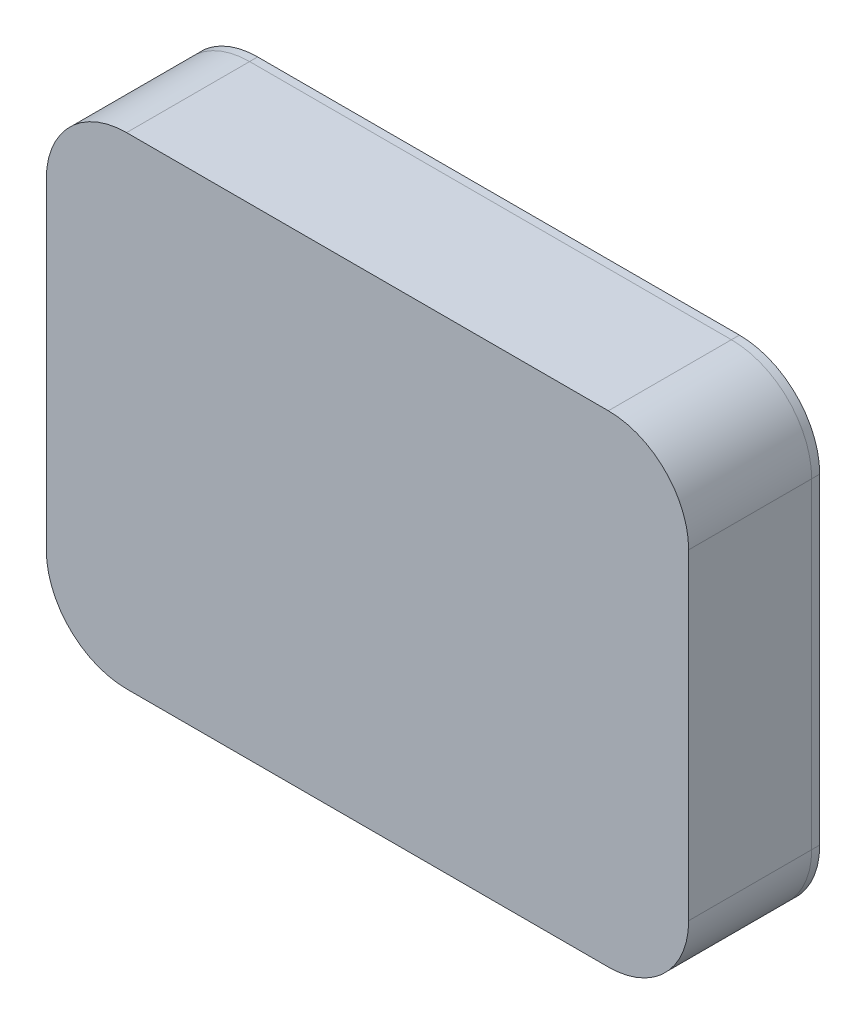
SolidWorks part; units mm, degrees
ref_plane "Plan de face" through (0, 0, 0) normal (0, 0, 1) x (1, 0, 0)
ref_plane "Plan de dessus" through (0, 0, 0) normal (0, 1, 0) x (1, 0, 0)
ref_plane "Plan de droite" through (0, 0, 0) normal (1, 0, 0) x (0, 0, -1)
sketch "Esquisse1" plane through (0, 0, 0) normal (0, 0, 1) x (1, 0, 0)
  line L1 (-30, 30) -> (30, 30)
  line L2 (-40, 20) -> (-40, -20)
  line L3 (-30, -30) -> (30, -30)
  line L4 (40, 20) -> (40, -20)
  line L5 (-40, 30) -> (40, -30) construction
  line L6 (-40, -30) -> (40, 30) construction
  arc A0 (-40, -20) -> (-30, -30) centre (-30, -20) ccw
  arc A1 (30, -30) -> (40, -20) centre (30, -20) ccw
  arc A2 (30, 30) -> (40, 20) centre (30, 20) cw
  arc A3 (-30, 30) -> (-40, 20) centre (-30, 20) ccw
  point P0 (0, 0)
  dimension "D1" = 10
  dimension "D2" = 40
  dimension "D3" = 60
sketch "profil" plane through (0, 0, 0) normal (1, 0, 0) x (0, 0, -1)
  line L0 (0, -28.4) -> (5.2972, -28.4)
  line L1 (5.2972, -28.4) -> (14.1228, -23.8)
  line L3 (14.1228, -30) -> (0, -30)
  line L4 (0, -30) -> (0, -28.4)
  line L6 (0, -20) -> (0, -30) construction
  line L7 (0, -30) -> (0, 30) construction
  line L8 (14.1228, -23.8) -> (14.1228, -25.4) construction
  line L9 (14.1228, -28.4) -> (14.1228, -30) construction
  line L10 (14.1228, -23.8) -> (15.1228, -23.8)
  line L11 (15.1228, -23.8) -> (15.1228, -25.4)
  line L12 (15.1228, -25.4) -> (14.1228, -25.4)
  line L13 (14.1228, -30) -> (15.1228, -30)
  line L14 (15.1228, -30) -> (15.1228, -28.4)
  line L15 (15.1228, -28.4) -> (14.1228, -28.4)
  line L16 (14.1228, -23.8) -> (14.1228, -30) construction
  arc A0 (14.1228, -25.4) -> (14.1228, -28.4) centre (14.1228, -26.9) ccw
  dimension "D1" = 3
  dimension "D3" = 14.1228
  dimension "D4" = 1
  dimension "D5" = 6.2
sweep "Balayage1" add profiles "profil" path "Esquisse1"
extrude "Boss.-Extru.1" add sketch "Esquisse1<3>" along normal blind 1.2
sketch "Esquisse1<3>" plane through (0, 0, 0) normal (0, 0, 1) x (1, 0, 0) same geometry as "Esquisse1"
fillet "Congé1" radius 2 9 edges at (-35.9397, 25.9397, 0) (-38.4, 0, 0) (-35.9397, -25.9397, 0) (-15, -28.4, 0) (15, -28.4, 0) (35.9397, -25.9397, 0) (38.4, 0, 0) (35.9397, 25.9397, 0) (0, 28.4, 0)
sketch "Esquisse2" plane through (0, 0, 0) normal (0, 0, -1) x (-1, 0, 0)
  circle A0 centre (-27.6661, 18.8186) radius 2.5
  circle A1 centre (-27.6661, -16.9814) radius 2.5
  circle A2 centre (19.6339, -17.0814) radius 2.5
  circle A3 centre (20.1225, 18.0592) radius 2.5
  dimension "D1" = 5
  dimension "D2" = 5
  dimension "D3" = 5
  dimension "D4" = 5
extrude "Plot" add sketch "Esquisse2" along normal blind 3
fillet "Congé2" radius 5 4 edges at (-17.1339, -17.0814, 0) (30.1661, -16.9814, 0) (-17.6225, 18.0592, 0) (30.1661, 18.8186, 0)
equation "\"buse\"=0.4"
equation "\"coque\"= \"buse\" * 4"
equation "\"diam_silicone\"=3"
equation "\"D1@profil\" = \"diam_silicone\""
equation "\"couche\"=0.2"
equation "\"D1@Boss.-Extru.1\"=\"fond\""
equation "\"fond\"= \"couche\" * 6"
equation "\"dim_ext\"= 40"
equation "\"D2@Esquisse1\"=\"dim_ext\""
equation "\"dim_ext_L\"=60"
equation "\"D3@Esquisse1\"=\"dim_ext_L\""
equation "\"hauteur_boitier\"=14.1228"
equation "\"D3@profil\"=\"hauteur_boitier\""
equation "\"epaisseur_jonction\"=6.2"
equation "\"D5@profil\"=\"epaisseur_jonction\""
